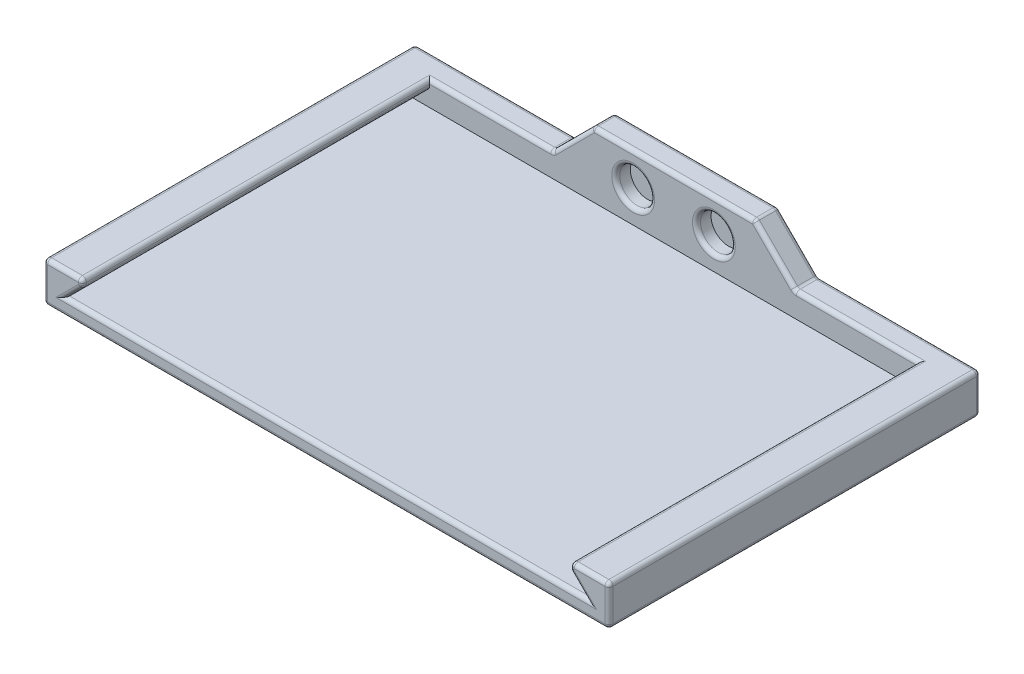
SolidWorks part; units mm, degrees
ref_plane "Front Plane" through (0, 0, 0) normal (0, 0, 1) x (1, 0, 0)
ref_plane "Top Plane" through (0, 0, 0) normal (0, 1, 0) x (1, 0, 0)
ref_plane "Right Plane" through (0, 0, 0) normal (1, 0, 0) x (0, 0, -1)
sketch "Sketch1" plane through (0, 0, 0) normal (0, 0, 1) x (1, 0, 0)
  line L1 (0, 3) -> (4.8, 3)
  line L4 (3, 0) -> (35, 0)
  line L5 (35, -2) -> (0, -2)
  line L7 (35, -2) -> (35, 0)
  line L8 (0, -2) -> (0, 3)
  line L9 (5, 3) -> (5, 2) construction
  line L10 (5, 2) -> (3, 0) construction
  line L11 (3, 0) -> (0, 0) construction
  line L12 (5, 2) -> (5, 0) construction
  line L13 (4.8, 3) -> (4.8, 2.0828)
  line L14 (4.8, 2.0828) -> (2.8586, 0.1414)
  line L15 (2.8586, 0.1414) -> (2.7172, 0)
  line L16 (2.7172, 0) -> (3, 0)
  line L17 (4.8, 3) -> (5, 3) construction
  line L18 (4.8, 3) -> (20, 3)
  line L19 (35, 3) -> (35, 0)
  line L20 (20, 3) -> (25, 8)
  line L21 (25, 8) -> (35, 8)
  line L22 (35, 8) -> (35, 3)
  line L23 (20, 3) -> (35, 3) construction
  line L24 (30, 8) -> (30, 0) construction
  circle A1 centre (30, 4) radius 2.15
  dimension "D11" = 4.3
  dimension "D1" = 2
  dimension "D2" = 5
  dimension "D3" = 3
  dimension "D4" = 5
  dimension "D5" = 1
  dimension "D6" = 2
  dimension "D8" = 35
  dimension "D9" = 5
  dimension "D10" = 10
  dimension "D7" = 0.2
extrude "Boss-Extrude1" add sketch "Sketch1" along normal blind 43 contours L16 L15 L14 L13 L1 L8 L5 L7 L4 region at (15.2091, -0.6069, 0)
extrude "Boss-Extrude2" add sketch "Sketch1<3>" against normal blind 3 contours L16 L15 L14 L13 L1 L8 L5 L7 L4 | A1 | L22 L21 L20 L18 L13 L14 L15 L16 L4 L19 A1 region at (15.2091, -0.6069, 0) region at (22.5074, 2.9319, 0) region at (30, 4, 0)
sketch "Sketch1<3>" plane through (0, 0, 0) normal (0, 0, 1) x (1, 0, 0) same geometry as "Sketch1"
extrude "Cut-Extrude1" cut sketch "Sketch1<5>" against normal blind 1.8 contours A1 region at (30, 4, 0)
sketch "Sketch1<5>" plane through (0, 0, 0) normal (0, 0, 1) x (1, 0, 0) same geometry as "Sketch1"
mirror "Mirror1" about plane through (35, 0, 43) normal (-1, 0, 0) of bodies 107 104
fillet "Fillet1" radius 0.5 37 edges at (47.5, 5.5, 0) (22.5, 5.5, 0) (66.2414, 1.0414, 43) (65.2, 2.5414, 43) (4.8, 2.5414, 43) (3.7586, 1.0414, 43) (35, 0, 43) (0, 0.5, 43) (70, 0.5, 43) (35, -2, 43) (70, -2, 20) (0, -2, 20) (22.5, 5.5, -3) (0, 0.5, -3) (35, -2, -3) (70, 0.5, -3) (47.5, 5.5, -3) (25, 8, -1.5) (35, 8, -3) (45, 8, -1.5) (35, 8, 0) (57.6, 3, 0) (50, 3, -1.5) (60, 3, -3) (70, 3, 20) (67.6, 3, 43) (65.2, 3, 21.5) (2.4, 3, 43) (0, 3, 20) (10, 3, -3) (20, 3, -1.5) (12.4, 3, 0) (4.8, 3, 21.5) (4.8, 2.0828, 21.5) (65.2, 2.0828, 21.5) (32.15, 4, 0) (37.85, 4, 0)
